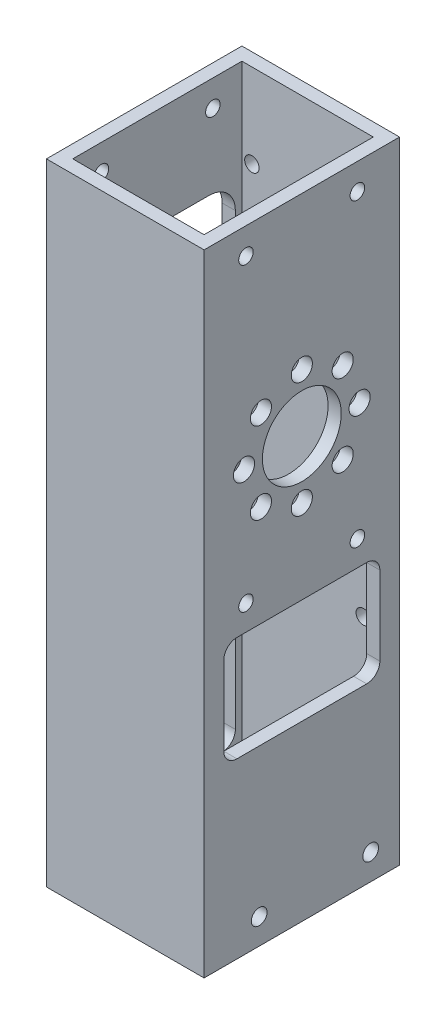
SolidWorks part; units mm, degrees
material "6061 Alloy"
ref_plane "Front" through (0, 0, 0) normal (0, 0, 1) x (1, 0, 0)
ref_plane "Top" through (0, 0, 0) normal (0, 1, 0) x (1, 0, 0)
ref_plane "Right" through (0, 0, 0) normal (1, 0, 0) x (0, 0, -1)
sketch "Sketch1" plane through (0, 0, 0) normal (0, 1, 0) x (1, 0, 0)
  line L0 (-15.875, 20.447) -> (15.875, 20.447)
  line L1 (-19.05, -23.622) -> (19.05, -23.622)
  line L2 (-19.05, -23.622) -> (-19.05, 23.622)
  line L3 (-19.05, 23.622) -> (19.05, 23.622)
  line L4 (19.05, -23.622) -> (19.05, 23.622)
  line L5 (-19.05, -23.622) -> (19.05, 23.622) construction
  line L6 (-19.05, 23.622) -> (19.05, -23.622) construction
  line L7 (15.875, -20.447) -> (15.875, 20.447)
  line L8 (-15.875, -20.447) -> (15.875, -20.447)
  line L9 (-15.875, -20.447) -> (-15.875, 20.447)
  point P0 (0, 0)
  dimension "D1" = 38.1
  dimension "D2" = 47.244
  dimension "D3" = 3.175
extrude "Boss-Extrude1" add sketch "Sketch1" along normal blind 152.4
sketch "Sketch2" plane through (15.875, 0, 0) normal (-1, 0, 0) x (0, 0, 1)
  circle A0 centre (-16.6454, 6.2154) radius 1.8986
  circle A1 centre (10.3003, 6.1824) radius 1.8986
  dimension "D1" = 3.7973
extrude "Cut-Extrude1" cut sketch "Sketch2" against normal through all both and the other way through all
sketch "Sketch4" plane through (-19.05, 0, 0) normal (-1, 0, 0) x (0, 0, 1)
  line L0 (-23.622, 152.4) -> (-23.622, 0) construction
  line L1 (15.6845, 10.16) -> (-15.6845, 10.16)
  line L2 (18.8595, 13.335) -> (18.8595, 64.135)
  line L3 (15.6845, 67.31) -> (-15.6845, 67.31)
  line L4 (-18.8595, 13.335) -> (-18.8595, 64.135)
  line L5 (18.8595, 10.16) -> (-18.8595, 67.31) construction
  line L6 (18.8595, 67.31) -> (-18.8595, 10.16) construction
  line L7 (23.622, 152.4) -> (23.622, 0) construction
  line L8 (-23.622, 0) -> (23.622, 0) construction
  arc A0 (-15.6845, 67.31) -> (-18.8595, 64.135) centre (-15.6845, 64.135) ccw
  arc A1 (18.8595, 64.135) -> (15.6845, 67.31) centre (15.6845, 64.135) ccw
  arc A2 (15.6845, 10.16) -> (18.8595, 13.335) centre (15.6845, 13.335) ccw
  arc A3 (-15.6845, 10.16) -> (-18.8595, 13.335) centre (-15.6845, 13.335) cw
  point P4 (0, 38.735)
  dimension "D4" = 3.175
  dimension "D1" = 4.7625
  dimension "D2" = 4.7625
  dimension "D3" = 10.16
  dimension "D5" = 57.15
extrude "Cut-Extrude3" cut sketch "Sketch4" against normal blind 3.175
sketch "Sketch5" plane through (19.05, 0, 0) normal (1, 0, 0) x (0, 0, -1)
  line L0 (23.622, 152.4) -> (23.622, 0) construction
  line L1 (15.6845, 67.31) -> (-15.6845, 67.31)
  line L2 (18.8595, 64.135) -> (18.8595, 45.085)
  line L3 (15.6845, 41.91) -> (-15.6845, 41.91)
  line L4 (-18.8595, 64.135) -> (-18.8595, 45.085)
  line L5 (18.8595, 67.31) -> (-18.8595, 41.91) construction
  line L6 (18.8595, 41.91) -> (-18.8595, 67.31) construction
  line L7 (-23.622, 152.4) -> (-23.622, 0) construction
  line L10 (23.622, 0) -> (-23.622, 0) construction
  arc A0 (-15.6845, 41.91) -> (-18.8595, 45.085) centre (-15.6845, 45.085) cw
  arc A1 (-15.6845, 67.31) -> (-18.8595, 64.135) centre (-15.6845, 64.135) ccw
  arc A2 (18.8595, 45.085) -> (15.6845, 41.91) centre (15.6845, 45.085) cw
  arc A3 (15.6845, 67.31) -> (18.8595, 64.135) centre (15.6845, 64.135) cw
  point P4 (0, 54.61)
  dimension "D5" = 3.175
  dimension "D1" = 4.7625
  dimension "D2" = 4.7625
  dimension "D3" = 67.31
  dimension "D4" = 25.4
extrude "Cut-Extrude4" cut sketch "Sketch5" against normal blind 3.175
sketch "Sketch6" plane through (15.875, 0, 0) normal (-1, 0, 0) x (0, 0, 1)
  line L0 (0, 101.6) -> (0, 0) construction
  line L1 (0, 87.63) -> (0, 101.6) construction
  circle A0 centre (0, 101.6) radius 9.525
  circle A1 centre (0, 87.63) radius 2.5527
  circle A2 centre (-9.8783, 91.7217) radius 2.5527
  circle A3 centre (-13.97, 101.6) radius 2.5527
  circle A4 centre (-9.8783, 111.4783) radius 2.5527
  circle A5 centre (0, 115.57) radius 2.5527
  circle A6 centre (9.8783, 111.4783) radius 2.5527
  circle A7 centre (13.97, 101.6) radius 2.5527
  circle A8 centre (9.8783, 91.7217) radius 2.5527
  point P22 (0, 101.6)
  dimension "D1" = 19.05
  dimension "D3" = 5.1054
  dimension "D2" = 101.6
  dimension "D4" = 13.97
  dimension "D6" = 0
  dimension "D5" = 8
extrude "Cut-Extrude5" cut sketch "Sketch6" against normal blind 3.175
sketch "Sketch7" plane through (-19.05, 0, 0) normal (-1, 0, 0) x (0, 0, 1)
  line L0 (23.622, 152.4) -> (23.622, 0) construction
  line L1 (-12.5095, 77.47) -> (12.5095, 77.47)
  line L2 (-18.8595, 83.82) -> (-18.8595, 121.92)
  line L3 (-12.5095, 128.27) -> (12.5095, 128.27)
  line L4 (18.8595, 83.82) -> (18.8595, 121.92)
  line L5 (-18.8595, 77.47) -> (18.8595, 128.27) construction
  line L6 (-18.8595, 128.27) -> (18.8595, 77.47) construction
  line L7 (-23.622, 152.4) -> (-23.622, 0) construction
  line L8 (16.51, 67.31) -> (-16.51, 67.31) construction
  arc A0 (-18.8595, 121.92) -> (-12.5095, 128.27) centre (-12.5095, 121.92) cw
  arc A1 (12.5095, 128.27) -> (18.8595, 121.92) centre (12.5095, 121.92) cw
  arc A2 (12.5095, 77.47) -> (18.8595, 83.82) centre (12.5095, 83.82) ccw
  arc A3 (-12.5095, 77.47) -> (-18.8595, 83.82) centre (-12.5095, 83.82) cw
  point P4 (0, 102.87)
  dimension "D5" = 6.35
  dimension "D1" = 50.8
  dimension "D2" = 4.7625
  dimension "D3" = 4.7625
  dimension "D4" = 10.16
extrude "Cut-Extrude6" cut sketch "Sketch7" against normal blind 3.175
sketch "Sketch8" plane through (19.05, 0, 0) normal (1, 0, 0) x (0, 0, -1)
  point P1 (-13.5004, 73.406)
  point P6 (13.4236, 146.05)
  point P7 (-13.5004, 146.05)
  point P9 (13.4236, 73.406)
hole_wizard "#6-32 Tapped Hole1" positions "3DSketch1" profile "Sketch9" tap size "#6-32" standard "ANSI Inch" end condition through all
sketch3d "3DSketch1"
  point P0 (19.05, 73.406, -13.4236)
  point P3 (19.05, 73.406, 13.5004)
  point P6 (19.05, 146.05, 13.5004)
  point P9 (19.05, 146.05, -13.4236)
sketch "Sketch9" plane through (19.05, 73.406, -13.4236) normal (0, 1, 0) x (0, 0, -1)
  line L0 (0, 0) -> (0, 38.1)
  line L1 (0, 38.1) -> (1.7526, 38.1)
  line L2 (1.7526, 38.1) -> (1.7526, 0)
  line L5 (1.7526, 0) -> (0, 0)
  line L11 (0, -6.35) -> (0, 107.95) construction
  dimension "Thread Major Dia." = 3.5052
  dimension "Thru Tap Drill Depth" = 38.1
sketch "Sketch11" plane through (0, 0, -23.622) normal (0, 0, -1) x (-1, 0, 0)
  line L0 (-5.5796, 136.6393) -> (5.5796, 136.6393) construction
  line L1 (0, 136.6393) -> (0, 152.4) construction
  line L2 (-19.05, 152.4) -> (19.05, 152.4) construction
sketch "Sketch15" plane through (0, 0, -23.622) normal (0, 0, -1) x (-1, 0, 0)
  line L0 (-13.462, 0) -> (-13.462, 152.4) construction
  line L1 (-19.05, 0) -> (19.05, 0) construction
  line L2 (-19.05, 152.4) -> (19.05, 152.4) construction
  line L3 (13.462, 152.4) -> (13.462, 0) construction
  line L4 (-19.05, 152.4) -> (-19.05, 0) construction
  line L5 (19.05, 152.4) -> (19.05, 0) construction
  line L6 (-13.462, 50.8) -> (13.462, 50.8) construction
  line L7 (-13.462, 76.2) -> (13.462, 76.2) construction
  line L8 (-13.462, 132.08) -> (13.462, 132.08) construction
  circle A0 centre (-13.462, 50.8) radius 1.7526
  circle A1 centre (13.462, 50.8) radius 1.7526
  circle A2 centre (-13.462, 76.2) radius 1.7526
  circle A3 centre (13.462, 76.2) radius 1.7526
  circle A4 centre (-13.462, 132.08) radius 1.7526
  circle A5 centre (13.462, 132.08) radius 1.7526
  dimension "D1" = 5.588
  dimension "D2" = 5.588
  dimension "D3" = 50.8
  dimension "D4" = 76.2
  dimension "D5" = 132.08
extrude "Cut-Extrude10" cut sketch "Sketch15" against normal up to next
